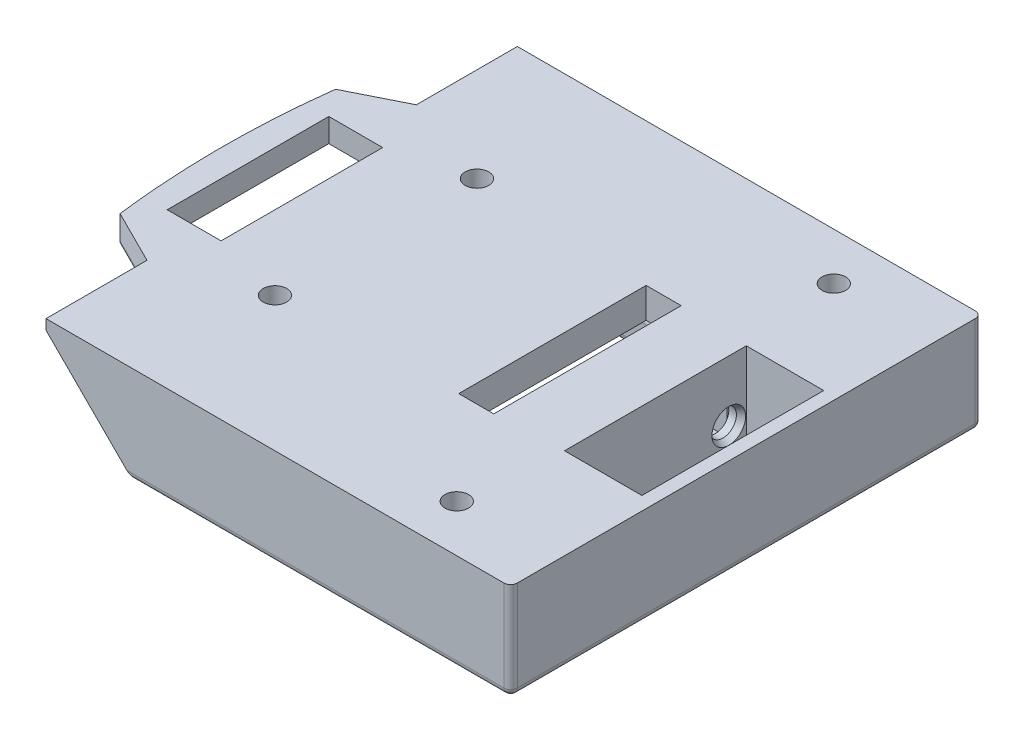
SolidWorks part; units mm, degrees
ref_plane "Front Plane" through (0, 0, 0) normal (0, 0, 1) x (1, 0, 0)
ref_plane "Top Plane" through (0, 0, 0) normal (0, 1, 0) x (1, 0, 0)
ref_plane "Right Plane" through (0, 0, 0) normal (1, 0, 0) x (0, 0, -1)
sketch "Sketch1" plane through (0, 0, 0) normal (0, 1, 0) x (1, 0, 0)
  line L0 (-32.8514, 19.25) -> (14.1486, 19.25)
  line L5 (14.1486, 19.25) -> (14.1486, 15)
  line L6 (14.1486, 15) -> (-1.3514, 15)
  line L7 (-1.3514, 15) -> (-1.3514, -15)
  line L8 (-1.3514, -15) -> (14.1486, -15)
  line L9 (14.1486, -15) -> (14.1486, -19.25)
  line L10 (14.1486, -19.25) -> (-32.8514, -19.25)
  line L11 (-32.8514, -19.25) -> (-32.8514, -35)
  line L12 (-32.8514, -35) -> (22.1486, -35)
  line L13 (22.1486, -35) -> (22.1486, 35)
  line L14 (22.1486, 35) -> (-32.8514, 35)
  line L15 (-32.8514, 35) -> (-32.8514, 19.25)
  point P10 (22.1486, 0)
  dimension "D1" = 38.5
  dimension "D2" = 30
  dimension "D3" = 55
  dimension "D4" = 23.5
  dimension "D5" = 70
  dimension "D6" = 8
extrude "Boss-Extrude2" add sketch "Sketch1" along normal blind 5
sketch "Sketch5" plane through (0, 5, 0) normal (0, 1, 0) x (1, 0, 0)
  line L0 (-32.8514, 35) -> (22.1486, 35)
  line L1 (22.1486, 35) -> (22.1486, -35)
  line L2 (22.1486, -35) -> (-32.8514, -35)
  line L3 (-32.8514, -35) -> (-32.8514, -23.5)
  line L4 (-32.8514, -19.25) -> (-32.8514, -35) construction
  line L5 (-32.8514, -23.5) -> (14.1486, -23.5)
  line L6 (14.1486, -23.5) -> (14.1486, -15)
  line L7 (14.1486, 23.5) -> (-32.8514, 23.5)
  line L8 (-32.8514, 35) -> (-32.8514, 19.25) construction
  line L9 (-32.8514, 23.5) -> (-32.8514, 35)
  line L10 (14.1486, -15) -> (-1.3514, -15)
  line L11 (-1.3514, -15) -> (-1.3514, 15)
  line L12 (-1.3514, 15) -> (14.1486, 15)
  line L13 (14.1486, 15) -> (14.1486, 23.5)
  dimension "D1" = 47
extrude "Boss-Extrude3" add sketch "Sketch5" along normal blind 5
sketch "Sketch6" plane through (0, 10, 0) normal (0, 1, 0) x (1, 0, 0)
  line L0 (-54.8514, 16) -> (-54.8514, -16) construction
  line L1 (22.1486, 35) -> (-46.8514, 35)
  line L2 (22.1486, 35) -> (22.1486, 23)
  line L3 (22.1486, -35) -> (-46.8514, -35)
  line L5 (-46.8514, 20) -> (-46.8514, -20) construction
  line L6 (-54.8514, 16) -> (-46.8514, 20)
  line L7 (-46.8514, 20) -> (-46.8514, 35)
  line L8 (-54.8514, -16) -> (-46.8514, -20)
  line L9 (-46.8514, -20) -> (-46.8514, -35)
  line L10 (22.1486, 23) -> (32.1486, 23) construction
  line L11 (32.1486, 23) -> (32.1486, -23) construction
  line L12 (32.1486, -23) -> (22.1486, -23) construction
  line L13 (22.1486, -23) -> (22.1486, -35)
  line L15 (-32.8514, -35) -> (22.1486, -35) construction
  line L16 (22.1486, 23) -> (22.1486, -23)
  spline S0 degree 2 poles (-54.8514, -16) (-56.8514, 0) (-54.8514, 16) knots 0 0 0 1 1 1
  point P7 (-54.8514, 0)
  point P12 (-46.8514, 0)
  dimension "D1" = 69
  dimension "D2" = 32
  dimension "D3" = 78
  dimension "D4" = 40
  dimension "D5" = 1
  dimension "D6" = 12
  dimension "D7" = 10
extrude "Boss-Extrude4" add sketch "Sketch6" along normal blind 4.5
chamfer "Chamfer1" distance 3 angle 45 2 edges at (-46.8514, 10, -27.5) (-46.8514, 10, 27.5)
sketch "Sketch7" plane through (0, 0, 35) normal (0, 0, 1) x (1, 0, 0)
  line L7 (-32.8514, 0) -> (22.1486, 0) construction
  line L8 (-33.8514, 0) -> (-43.8514, 10)
  line L9 (-33.8514, 0) -> (-32.8514, 0)
  line L10 (-32.8514, 0) -> (-32.8514, 10)
  line L12 (-32.8514, 10) -> (-43.8514, 10)
  line L13 (-43.8514, 10) -> (-32.8514, 10) construction
  dimension "D1" = 45
extrude "Boss-Extrude5" add sketch "Sketch7" against normal up to surface (11.5 mm away) up to face at (-9.3514, 7.5, 23.5)
sketch "Sketch8" plane through (0, 0, -35) normal (0, 0, -1) x (-1, 0, 0)
  line L0 (43.8514, 10) -> (33.8514, 0)
  line L1 (33.8514, 0) -> (32.8514, 0)
  line L2 (32.8514, 0) -> (32.8514, 10)
  line L3 (-14.1486, 10) -> (43.8514, 10) construction
  line L4 (32.8514, 10) -> (43.8514, 10) construction
  line L5 (32.8514, 10) -> (43.8514, 10)
extrude "Boss-Extrude6" add sketch "Sketch8" against normal up to surface (11.5 mm away) up to face at (-9.3514, 7.5, -23.5)
chamfer "Chamfer7" [suppressed] distance 5 angle 45
fillet "Fillet2" radius 1 12 edges at (-9.3514, 0, 19.25) (-1.3514, 5, 15) (-1.3514, 5, -15) (-1.3514, 0, 0) (-9.3514, 5, -19.25) (-9.3514, 0, -19.25) (-5.8514, 0, -35) (22.1486, 0, 0) (-5.8514, 0, 35) (-9.3514, 5, 19.25) (22.1486, 7.25, -35) (22.1486, 7.25, 35)
chamfer "Chamfer11" [suppressed] distance 5 angle 45
sketch "Sketch11" plane through (0, 10, 0) normal (0, -1, 0) x (1, 0, 0)
  line L0 (22.1486, 34) -> (22.1486, -34) construction
  line L1 (-51.8514, 12) -> (-43.8514, 12)
  line L2 (-51.8514, 12) -> (-51.8514, -12)
  line L3 (-51.8514, -12) -> (-43.8514, -12)
  line L4 (-43.8514, 12) -> (-43.8514, -12)
  point P6 (-51.8514, 0)
  dimension "D1" = 66
  dimension "D2" = 8
  dimension "D3" = 24
extrude "Cut-Extrude6" cut sketch "Sketch11" against normal through all
sketch "Sketch12" plane through (0, 0, 0) normal (0, -1, 0) x (1, 0, 0)
  line L1 (8.6486, 13.5) -> (20.1486, 13.5)
  line L2 (8.6486, 13.5) -> (8.6486, 7)
  line L3 (8.6486, -13.5) -> (20.1486, -13.5)
  line L4 (20.1486, 13.5) -> (20.1486, -13.5)
  line L5 (22.1486, 34) -> (22.1486, -34) construction
  line L6 (-1.3514, -14) -> (-1.3514, 14) construction
  line L10 (8.6486, -7) -> (8.6486, -13.5)
  line L11 (8.6486, 7) -> (8.6486, -7)
  dimension "D1" = 27
  dimension "D2" = 2
  dimension "D3" = 10
extrude "Cut-Extrude7" cut sketch "Sketch12" against normal through all from offset 1 offset against normal yes
sketch "Sketch13" plane through (-1.3514, 0, 0) normal (-1, 0, 0) x (0, 0, 1)
  line L0 (11.4, 2.1716) -> (11.4, 2.25)
  line L1 (-12.6, 8.75) -> (-11.4, 8.75)
  line L2 (-12.6, 8.75) -> (-12.6, 2.25)
  line L3 (-12.6, 2.25) -> (-11.4, 2.25)
  line L4 (-11.4, 8.75) -> (-11.4, 7.5)
  line L17 (12.6, 2.25) -> (11.4, 2.25)
  line L18 (0, 10) -> (0, 1) construction
  line L19 (-14, 1) -> (14, 1) construction
  line L20 (-16, 10) -> (16, 10) construction
  line L23 (-11.4, 2.1716) -> (-11.4, 2.25)
  line L32 (-11.4, 2.1716) -> (-9.4858, 4.0858)
  line L33 (-10.9, 7.5) -> (-11.4, 7.5)
  line L34 (12.6, 8.75) -> (12.6, 2.25)
  line L35 (12.6, 8.75) -> (11.4, 8.75)
  line L36 (11.4, 8.75) -> (11.4, 7.5)
  line L37 (10.9, 7.5) -> (11.4, 7.5)
  line L38 (11.4, 2.1716) -> (9.4858, 4.0858)
  arc A0 (-9.4858, 4.0858) -> (-10.9, 7.5) centre (-10.9, 5.5) ccw
  arc A2 (9.4858, 4.0858) -> (10.9, 7.5) centre (10.9, 5.5) cw
  point P4 (-12, 2.25)
  point P6 (0, 5.5)
  point P15 (-12.6, 5.5)
  dimension "D4" = 4
  dimension "D1" = 12
  dimension "D2" = 1.2
  dimension "D3" = 6.5
  dimension "D5" = 0.5
  dimension "D6" = 45
extrude "Cut-Extrude8" cut sketch "Sketch13" against normal blind 8
fillet "Fillet3" radius 1 3 edges at (-49.3514, 10, 18.75) (-49.3514, 10, -18.75)
fillet "Fillet4" [suppressed] radius 1
chamfer "Chamfer9" distance 1 angle 45 4 edges at (-47.8514, 10, -12) (-43.8514, 10, 0) (-47.8514, 10, 12) (-51.8514, 10, 0)
sketch "Sketch14" plane through (0, 10, 0) normal (0, -1, 0) x (1, 0, 0)
  line L0 (-32.8514, 0) -> (-32.8514, 15) construction
  line L1 (-32.8514, 0) -> (-32.8514, -15) construction
  line L2 (22.1486, 34) -> (22.1486, -34) construction
  line L3 (-32.8514, -15) -> (27.1486, -15) construction
  line L4 (27.1486, -15) -> (27.1486, 15) construction
  line L5 (27.1486, 15) -> (-32.8514, 15) construction
  line L6 (7.1486, 28) -> (7.1486, -28) construction
  circle A0 centre (-32.8514, 15) radius 1.75
  circle A1 centre (-32.8514, -15) radius 1.75
  circle A2 centre (27.1486, -15) radius 1.75
  circle A3 centre (27.1486, 15) radius 1.75
  circle A4 centre (7.1486, 28) radius 1.75
  circle A5 centre (7.1486, -28) radius 1.75
  point P16 (7.1486, 0)
  dimension "D1" = 3.5
  dimension "D2" = 55
  dimension "D5" = 40
  dimension "D3" = 30
  dimension "D4" = 60
  dimension "D6" = 56
extrude "Cut-Extrude9" cut sketch "Sketch14" against normal through all both and the other way through all
chamfer "Chamfer10" distance 2 angle 45 4 edges at (-32.8514, 10, -13.25) (-32.8514, 10, 16.75) (7.1486, 0, -29.75) (7.1486, 0, 26.25)
chamfer "Chamfer8" distance 3 angle 45 2 edges at (-32.8514, 2.5, -19.25) (-32.8514, 2.5, 19.25)
sketch "Sketch16" plane through (0, 10, 0) normal (0, -1, 0) x (1, 0, 0)
  line L1 (-1.3514, 14) -> (-6.5613, 14)
  line L2 (-1.3514, 14) -> (-1.3514, -13.8355)
  line L3 (-1.3514, -13.8355) -> (-6.5613, -13.8355)
  line L4 (-6.5613, 14) -> (-6.5613, -13.8355)
extrude "Cut-Extrude10" cut sketch "Sketch16" against normal through all
sketch "Sketch17" plane through (6.6486, 0, 0) normal (-1, 0, 0) x (0, 0, 1)
  line L0 (0, -7.975) -> (0, 7.975) construction
  circle A0 centre (-10.9, 5.5) radius 2
  circle A1 centre (10.9, 5.5) radius 2
  dimension "D1" = 4
extrude "Cut-Extrude11" cut sketch "Sketch17" against normal up to next
chamfer "Chamfer12" distance 0.5 angle 60 2 edges at (8.6486, 5.5, -8.9) (8.6486, 5.5, 12.9) first distance on face at (8.6486, 5.5, -8.9)
